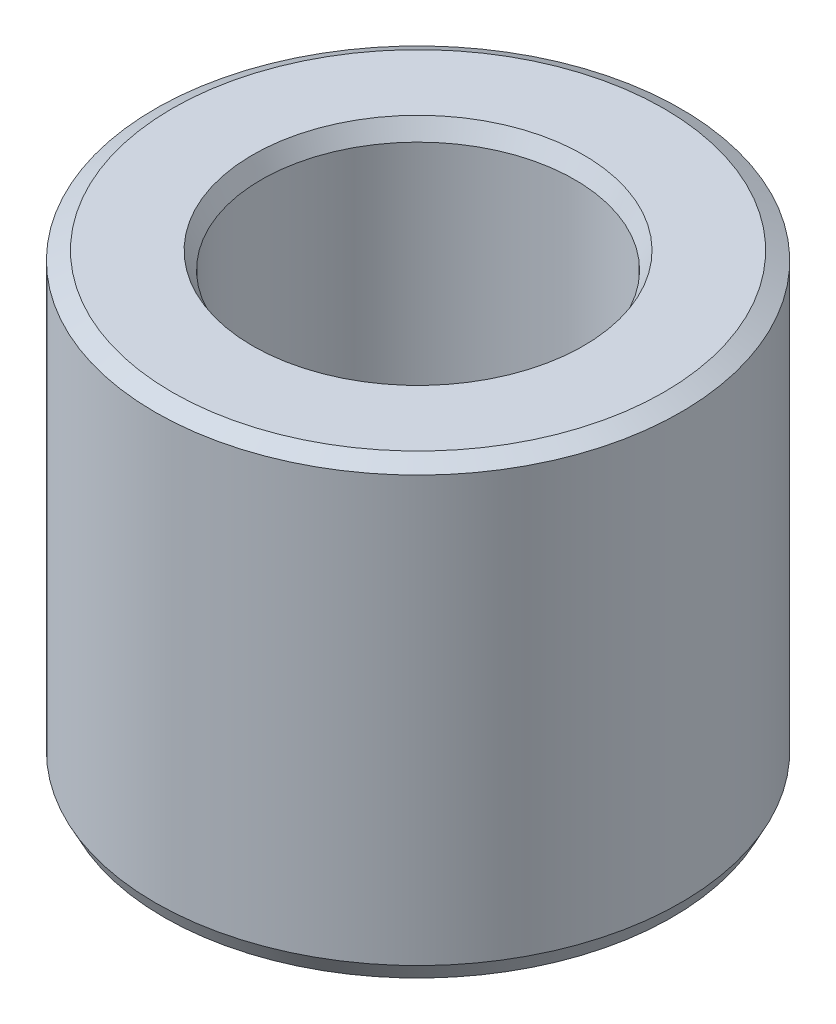
SolidWorks part; units mm, degrees
ref_plane "Front Plane" through (0, 0, 0) normal (0, 0, 1) x (1, 0, 0)
ref_plane "Top Plane" through (0, 0, 0) normal (0, 1, 0) x (1, 0, 0)
ref_plane "Right Plane" through (0, 0, 0) normal (1, 0, 0) x (0, 0, -1)
sketch "Sketch1" plane through (0, 0, 0) normal (0, 1, 0) x (1, 0, 0)
  circle A0 centre (0, 0) radius 40
  dimension "SLEEVE_OD" = 80
extrude "Boss-Extrude1" add sketch "Sketch1" along normal blind 68.5759
sketch "Sketch2" plane through (0, 0, 0) normal (0, 1, 0) x (1, 0, 0)
  circle A0 centre (0, 0) radius 23.8427
  dimension "BORE_D" = 47.6854
extrude "Cut-Extrude1" cut sketch "Sketch2" along normal through all
chamfer "Chamfer1" distance 1.3389 angle 62.666 4 edges at (0, 68.5759, 23.8427) (0, 0, 23.8427) (0, 0, 40) (0, 68.5759, 40) first distance on face at (0, 68.5759, 23.8427) first distance on face at (0, 0, 23.8427) first distance on face at (0, 68.5759, 40)
